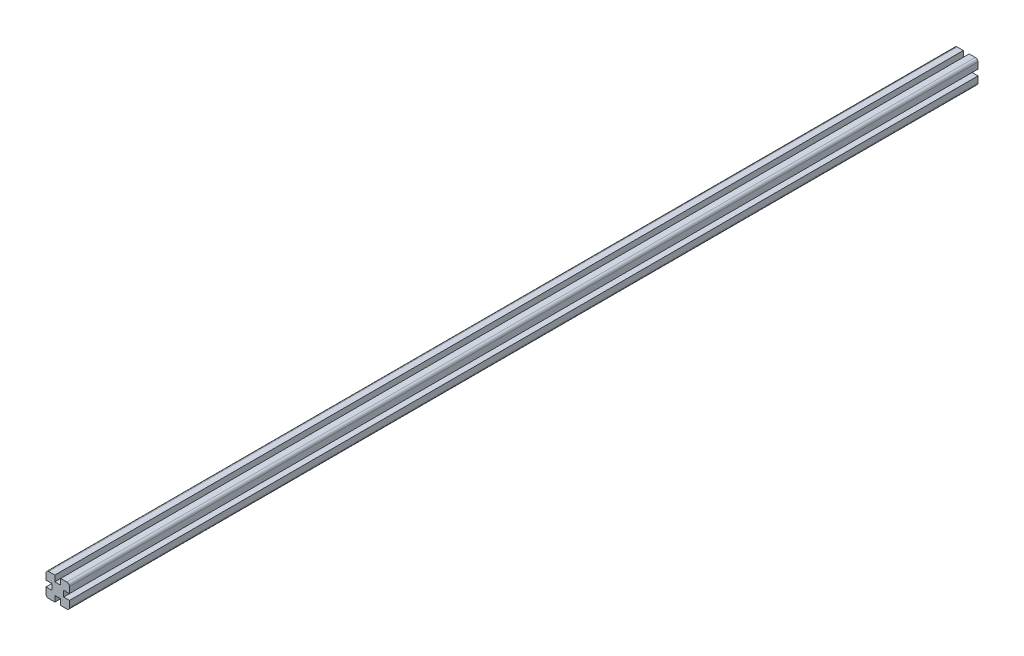
SolidWorks part; units mm, degrees
ref_plane "Front Plane" through (0, 0, 0) normal (0, 0, 1) x (1, 0, 0)
ref_plane "Top Plane" through (0, 0, 0) normal (0, 1, 0) x (1, 0, 0)
ref_plane "Right Plane" through (0, 0, 0) normal (1, 0, 0) x (0, 0, -1)
sketch "Sketch1" plane through (0, 0, 0) normal (0, 0, 1) x (1, 0, 0)
  line L0 (0, 0) -> (0, -50000) construction
  line L1 (-15.5, -20) -> (-5, -20)
  line L2 (-20, -15.5) -> (-20, -5)
  line L3 (-15.5, 20) -> (-15, 20)
  line L4 (20, -15.5) -> (20, -5)
  line L5 (-20, -20) -> (20, 20) construction
  line L6 (-20, 20) -> (20, -20) construction
  line L8 (-5, -20) -> (-5, -10)
  line L9 (-5, -10) -> (5, -10)
  line L10 (5, -20) -> (5, -10)
  line L15 (5, -20) -> (15.5, -20)
  line L16 (-8, 20) -> (-5, 20)
  line L18 (-15, 20) -> (-8, 20)
  line L19 (-20, 5) -> (-10, 5)
  line L20 (-10, 5) -> (-10, -5)
  line L21 (-20, -5) -> (-10, -5)
  line L22 (5, 20) -> (5, 10)
  line L23 (5, 10) -> (-5, 10)
  line L24 (-5, 20) -> (-5, 10)
  line L25 (20, -5) -> (10, -5)
  line L26 (10, -5) -> (10, 5)
  line L27 (20, 5) -> (10, 5)
  line L28 (-20, 5) -> (-20, 15.5)
  line L29 (5, 20) -> (15.5, 20)
  line L30 (20, 5) -> (20, 15.5)
  arc A0 (-20, 15.5) -> (-15.5, 20) centre (-15.5, 15.5) cw
  arc A1 (-15.5, -20) -> (-20, -15.5) centre (-15.5, -15.5) cw
  arc A2 (15.5, -20) -> (20, -15.5) centre (15.5, -15.5) ccw
  arc A3 (15.5, 20) -> (20, 15.5) centre (15.5, 15.5) cw
  point P0 (0, 0)
  point P11 (-12.3022, 2.8043)
  point P12 (0, 0)
  point P41 (0, 0)
  dimension "D8" = 4.5
  dimension "D1" = 40
  dimension "D2" = 40
  dimension "D3" = 15
  dimension "D4" = 10
  dimension "D5" = 5
  dimension "D6" = 28
  dimension "D7" = 4
extrude "Boss-Extrude1" add sketch "Sketch1" along normal blind 1550
